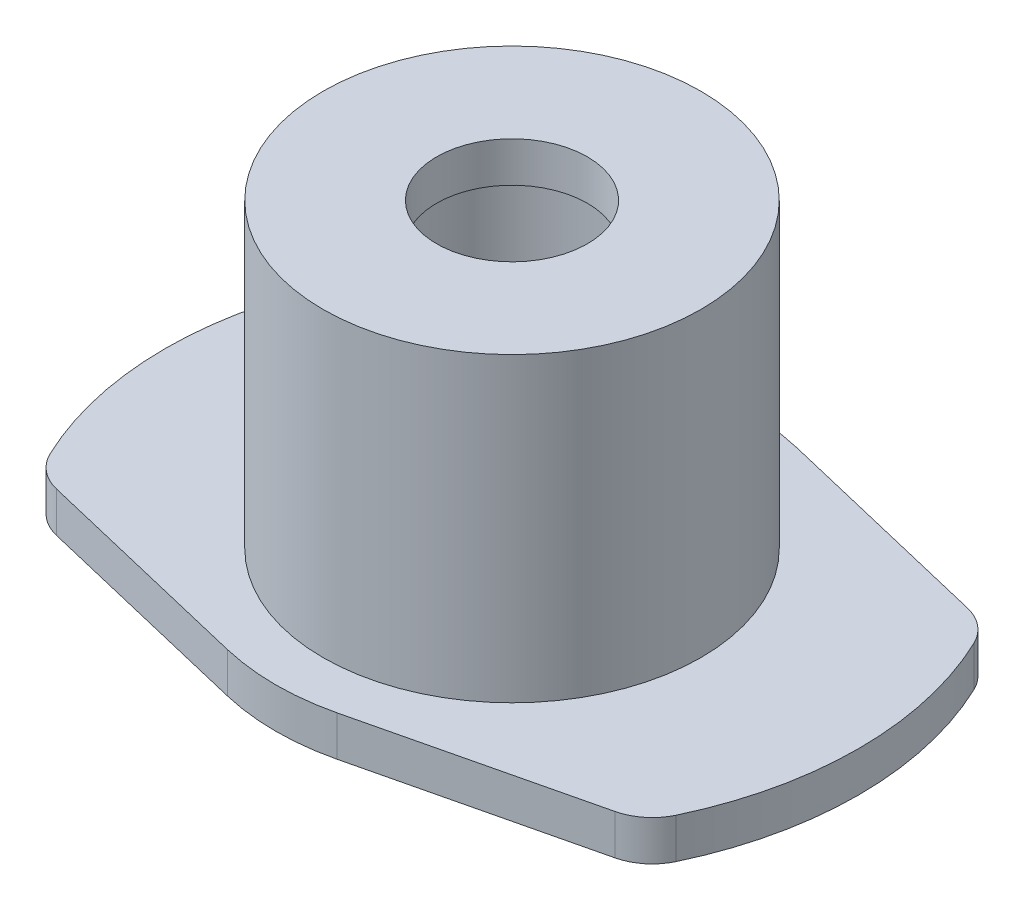
SolidWorks part; units mm, degrees
ref_plane "Front Plane" through (0, 0, 0) normal (0, 0, 1) x (1, 0, 0)
ref_plane "Top Plane" through (0, 0, 0) normal (0, 1, 0) x (1, 0, 0)
ref_plane "Right Plane" through (0, 0, 0) normal (1, 0, 0) x (0, 0, -1)
sketch "Sketch1" plane through (0, 0, 0) normal (0, 1, 0) x (1, 0, 0)
  line L0 (-15, 8.5) -> (-2.7277, 11.429)
  line L1 (-15, -8.5) -> (15, -8.5) construction
  line L2 (-15, -8.5) -> (-15, 8.5) construction
  line L3 (-15, 8.5) -> (15, 8.5) construction
  line L4 (15, -8.5) -> (15, 8.5) construction
  line L5 (-15, -8.5) -> (15, 8.5) construction
  line L6 (-15, 8.5) -> (15, -8.5) construction
  line L7 (15, 8.5) -> (2.7277, 11.429)
  line L8 (-15, -8.5) -> (-2.7277, -11.429)
  line L9 (15, -8.5) -> (2.7277, -11.429)
  arc A0 (-2.7277, -11.429) -> (2.7277, -11.429) centre (0, 0) ccw
  arc A1 (-15, 8.5) -> (-15, -8.5) centre (0, 0) ccw
  arc A2 (15, -8.5) -> (15, 8.5) centre (0, 0) ccw
  arc A3 (2.7277, 11.429) -> (-2.7277, 11.429) centre (0, 0) ccw
  point P0 (0, 0)
  dimension "D3" = 23.5
  dimension "D1" = 17
  dimension "D2" = 30
extrude "Boss-Extrude1" add sketch "Sketch1" along normal blind 2
sketch "Sketch2" plane through (0, 2, 0) normal (0, 1, 0) x (1, 0, 0)
  circle A0 centre (0, 0) radius 9.4
  dimension "D1" = 18.8
extrude "Boss-Extrude2" add sketch "Sketch2" along normal blind 15
sketch "Sketch3" plane through (0, 0, 0) normal (0, -1, 0) x (1, 0, 0)
  circle A0 centre (0, 0) radius 5.1
  dimension "D1" = 10.2
extrude "Cut-Extrude1" cut sketch "Sketch3" against normal blind 15
sketch "Sketch4" plane through (0, 15, 0) normal (0, -1, 0) x (1, 0, 0)
  circle A0 centre (0, 0) radius 3.75
  dimension "D1" = 7.5
extrude "Cut-Extrude2" cut sketch "Sketch4" against normal through all
fillet "Fillet1" radius 2.5 4 edges at (-15, 1, 8.5) (15, 1, -8.5) (15, 1, 8.5) (-15, 1, -8.5)
equation "\"`7\"=19"
